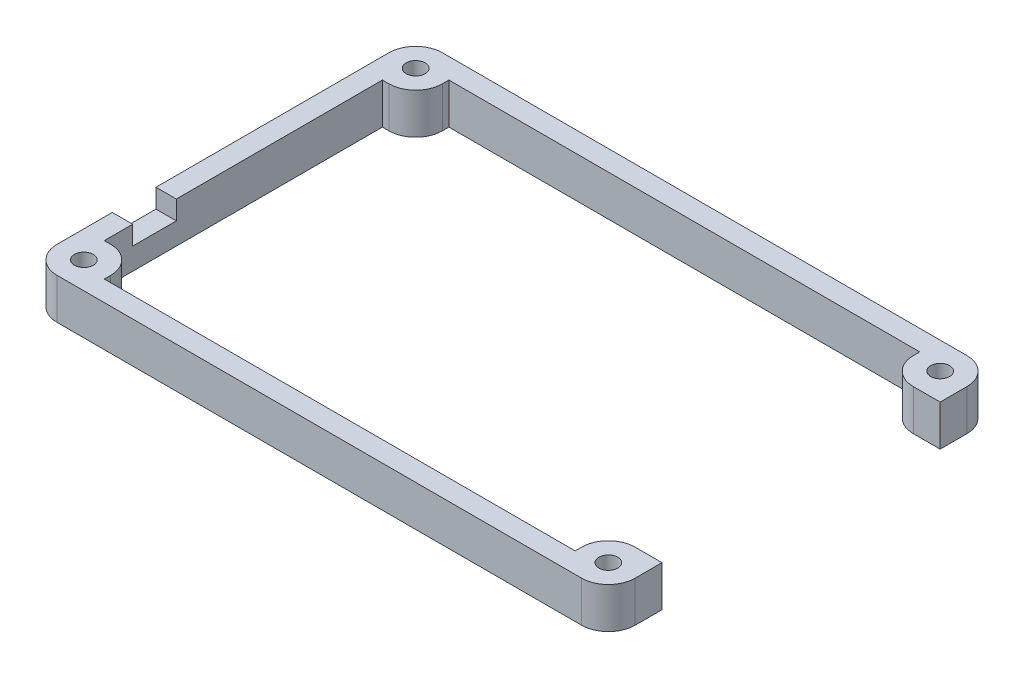
SolidWorks part; units mm, degrees
material "Rubber"
ref_plane "Front" through (0, 0, 0) normal (0, 0, 1) x (1, 0, 0)
ref_plane "Top" through (0, 0, 0) normal (0, 1, 0) x (1, 0, 0)
ref_plane "Right" through (0, 0, 0) normal (1, 0, 0) x (0, 0, -1)
sketch "Sketch1" plane through (0, 0, 0) normal (0, 1, 0) x (1, 0, 0)
  line L0 (-45, 0) -> (45, 0) construction
  line L1 (-45, 30) -> (45, 30) construction
  line L2 (-45, 30) -> (-45, -30) construction
  line L3 (-45, -30) -> (45, -30) construction
  line L4 (45, 30) -> (45, -30) construction
  line L5 (0, -30) -> (0, 30) construction
  line L6 (41.825, 26.825) -> (41.825, -26.825) construction
  line L7 (-41.825, -26.825) -> (41.825, -26.825) construction
  line L8 (-41.825, 26.825) -> (-41.825, -26.825) construction
  line L9 (-41.825, 26.825) -> (41.825, 26.825) construction
  line L10 (40.825, 25.825) -> (40.825, -25.825) construction
  line L11 (-40.825, -25.825) -> (40.825, -25.825) construction
  line L12 (-40.825, 25.825) -> (-40.825, -25.825) construction
  line L13 (-40.825, 25.825) -> (40.825, 25.825) construction
  line L14 (40.825, 21.65) -> (45, 21.65) construction
  line L15 (40.825, -21.65) -> (45, -21.65) construction
  line L16 (36.65, -25.825) -> (36.65, -30) construction
  line L17 (-36.65, -25.825) -> (-36.65, -30) construction
  line L18 (-40.825, -21.65) -> (-45, -21.65) construction
  line L19 (-36.65, 25.825) -> (-36.65, 30) construction
  line L20 (-40.825, 21.65) -> (-45, 21.65) construction
  line L21 (36.65, 25.825) -> (36.65, 30) construction
  line L22 (40.825, -25.825) -> (41.825, -25.825) construction
  circle A0 centre (-40.825, -25.825) radius 1 construction
  circle A1 centre (40.825, -25.825) radius 1 construction
  circle A2 centre (40.825, 25.825) radius 1 construction
  circle A3 centre (-40.825, 25.825) radius 1 construction
  circle A4 centre (40.825, -25.825) radius 4.175 construction
  circle A5 centre (40.825, 25.825) radius 4.175 construction
  circle A6 centre (-40.825, 25.825) radius 4.175 construction
  circle A7 centre (-40.825, -25.825) radius 4.175 construction
  dimension "D1" = 90
  dimension "D2" = 60
  dimension "D4" = 1
  dimension "D3" = 3.175
sketch "Sketch2" plane through (0, 0, 0) normal (0, 1, 0) x (1, 0, 0)
  line L0 (-45, 30) -> (-45, -30) construction
  line L1 (-45, -30) -> (45, -30) construction
  line L2 (45, 30) -> (45, -30) construction
  line L3 (-45, 30) -> (45, 30) construction
  line L4 (40.825, 21.65) -> (45, 21.65) construction
  line L5 (36.65, 25.825) -> (36.65, 30) construction
  line L6 (-36.65, 25.825) -> (-36.65, 30) construction
  line L7 (-40.825, 21.65) -> (-45, 21.65) construction
  line L8 (-36.65, -25.825) -> (-36.65, -30) construction
  line L9 (-40.825, -21.65) -> (-45, -21.65) construction
  line L10 (36.65, -25.825) -> (36.65, -30) construction
  line L11 (40.825, -21.65) -> (45, -21.65) construction
  line L16 (-45, 25.825) -> (-45, -25.825)
  line L17 (-40.825, -30) -> (40.825, -30)
  line L18 (45, 25.825) -> (45, -25.825)
  line L19 (-40.825, 30) -> (40.825, 30)
  line L20 (40.825, 21.65) -> (41.825, 21.65)
  line L21 (36.65, 25.825) -> (36.65, 26.825)
  line L22 (-36.65, 25.825) -> (-36.65, 26.825)
  line L23 (-40.825, 21.65) -> (-41.825, 21.65)
  line L24 (-36.65, -25.825) -> (-36.65, -26.825)
  line L25 (-40.825, -21.65) -> (-41.825, -21.65)
  line L26 (36.65, -25.825) -> (36.65, -26.825)
  line L27 (40.825, -21.65) -> (41.825, -21.65)
  line L28 (41.825, 26.825) -> (41.825, -26.825) construction
  line L29 (-36.65, -26.825) -> (36.65, -26.825)
  line L30 (-41.825, 26.825) -> (41.825, 26.825) construction
  line L31 (-41.825, 26.825) -> (-41.825, -26.825) construction
  line L32 (-36.65, 26.825) -> (36.65, 26.825)
  line L33 (-41.825, 21.65) -> (-41.825, -21.65)
  line L34 (41.825, 21.65) -> (41.825, -21.65)
  line L35 (-41.825, -26.825) -> (41.825, -26.825) construction
  circle A0 centre (40.825, 25.825) radius 4.175 construction
  circle A1 centre (40.825, 25.825) radius 1 construction
  circle A2 centre (-40.825, 25.825) radius 4.175 construction
  circle A3 centre (-40.825, 25.825) radius 1 construction
  circle A4 centre (-40.825, -25.825) radius 4.175 construction
  circle A5 centre (40.825, -25.825) radius 4.175 construction
  arc A6 (45, 25.825) -> (40.825, 30) centre (40.825, 25.825) ccw
  circle A7 centre (40.825, 25.825) radius 1 construction
  arc A8 (-40.825, 30) -> (-45, 25.825) centre (-40.825, 25.825) ccw
  circle A9 centre (-40.825, 25.825) radius 1 construction
  arc A10 (-36.65, -25.825) -> (-40.825, -21.65) centre (-40.825, -25.825) ccw
  arc A11 (40.825, -21.65) -> (36.65, -25.825) centre (40.825, -25.825) ccw
  circle A12 centre (-40.825, -25.825) radius 1 construction
  circle A13 centre (40.825, -25.825) radius 1 construction
  circle A14 centre (-40.825, -25.825) radius 1 construction
  circle A15 centre (40.825, -25.825) radius 1 construction
  arc A16 (-40.825, 21.65) -> (-36.65, 25.825) centre (-40.825, 25.825) ccw
  arc A17 (-45, -25.825) -> (-40.825, -30) centre (-40.825, -25.825) ccw
  arc A18 (40.825, -30) -> (45, -25.825) centre (40.825, -25.825) ccw
  arc A19 (36.65, 25.825) -> (40.825, 21.65) centre (40.825, 25.825) ccw
extrude "Boss-Extrude3" add sketch "Sketch2" along normal blind 6.35
sketch "Antenna Hole Size" plane through (-45, 0, 0) normal (-1, 0, 0) x (0, 0, 1)
  line L0 (13.825, 6.35) -> (25.825, 6.35) construction
  line L1 (25.825, 6.35) -> (25.825, 0) construction
  line L3 (10.425, 9.3) -> (17.225, 9.3)
  line L4 (10.425, 9.3) -> (10.425, 3.4)
  line L5 (10.425, 3.4) -> (17.225, 3.4)
  line L6 (17.225, 9.3) -> (17.225, 3.4)
  line L7 (10.425, 9.3) -> (17.225, 3.4) construction
  line L8 (10.425, 3.4) -> (17.225, 9.3) construction
  dimension "D1" = 12
  dimension "D2" = 5.9
  dimension "D3" = 6.8
extrude "Cut-Extrude3" cut sketch "Antenna Hole Size" against normal up to surface (3.175 mm away) up to face at (-41.825, 3.175, 0)
sketch "Sketch7" plane through (0, 0, 0) normal (0, -1, 0) x (1, 0, 0)
  circle A0 centre (-40.825, -25.825) radius 1.4732
  circle A1 centre (-40.825, 25.825) radius 1.4732
  circle A2 centre (40.825, 25.825) radius 1.4732
  circle A3 centre (40.825, -25.825) radius 1.4732
  dimension "D1" = 2.9464
  dimension "D2" = 2.9464
  dimension "D3" = 2.9464
  dimension "D4" = 2.9464
extrude "Cut-Extrude4" cut sketch "Sketch7" against normal blind 10
sketch "Sketch8" plane through (0, 6.35, 0) normal (0, 1, 0) x (1, 0, 0)
  line L0 (45, -25.825) -> (45, 25.825) construction
  line L1 (45, 21.65) -> (41.825, 21.65)
  line L2 (45, 21.65) -> (45, -21.65)
  line L3 (45, -21.65) -> (41.825, -21.65)
  line L4 (41.825, 21.65) -> (41.825, -21.65)
  line L5 (45, 21.65) -> (41.825, -21.65) construction
  line L6 (45, -21.65) -> (41.825, 21.65) construction
  point P0 (43.4125, 0)
extrude "Cut-Extrude5" cut sketch "Sketch8" against normal through all
sketch "Sketch9" plane through (-45, 0, 0) normal (-1, 0, 0) x (0, 0, 1)
  line L0 (10.425, 6.35) -> (17.225, 6.35) construction
  line L1 (13.825, 6.35) -> (13.825, 3.4) construction
  line L2 (10.425, 3.4) -> (17.225, 3.4) construction
